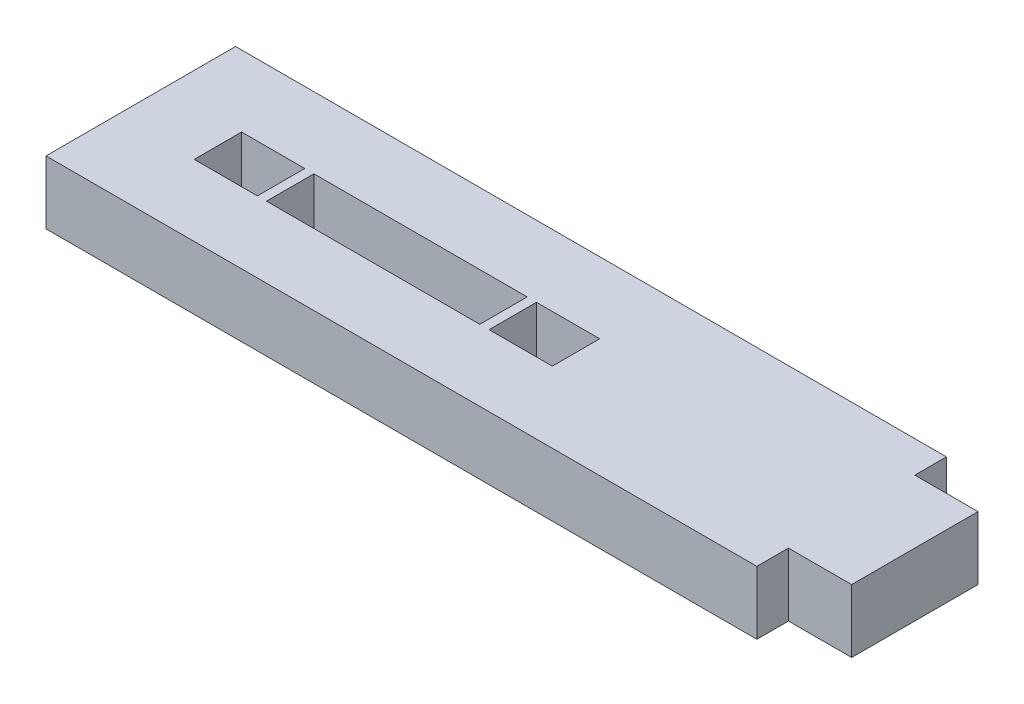
SolidWorks part; units mm, degrees
ref_plane "Front Plane" through (0, 0, 0) normal (0, 0, 1) x (1, 0, 0)
ref_plane "Top Plane" through (0, 0, 0) normal (0, 1, 0) x (1, 0, 0)
ref_plane "Right Plane" through (0, 0, 0) normal (1, 0, 0) x (0, 0, -1)
sketch "Sketch1" plane through (0, 0, 0) normal (0, 1, 0) x (1, 0, 0)
  line L1 (-22.5, -6) -> (22.5, -6)
  line L2 (-22.5, -6) -> (-22.5, 6)
  line L3 (-22.5, 6) -> (22.5, 6)
  line L4 (22.5, -6) -> (22.5, 6)
  line L5 (0, 6) -> (0, -6) construction
  line L6 (-22.5, 0) -> (22.5, 0) construction
  point P0 (0, 0)
  dimension "D1" = 45
  dimension "D2" = 12
extrude "Boss-Extrude1" add sketch "Sketch1" along normal blind 4
sketch "Sketch2" plane through (0, 0, 0) normal (0, 1, 0) x (1, 0, 0)
  line L0 (22.5, -6) -> (22.5, 6) construction
  line L1 (18.5, -4) -> (26.5, -4)
  line L2 (18.5, -4) -> (18.5, 4)
  line L3 (18.5, 4) -> (26.5, 4)
  line L4 (26.5, -4) -> (26.5, 4)
  line L5 (22.5, 4) -> (22.5, -4) construction
  line L6 (18.5, 0) -> (26.5, 0) construction
  point P0 (22.5, 0)
  dimension "D1" = 4
  dimension "D2" = 8
extrude "Boss-Extrude2" add sketch "Sketch2" along normal blind 4
sketch "Sketch4" plane through (0, 0, 0) normal (0, 1, 0) x (1, 0, 0)
  line L0 (-4.9, 6) -> (-4.9, -6) construction
  line L1 (22.5, 6) -> (-22.5, 6) construction
  line L2 (-22.5, -6) -> (22.5, -6) construction
  line L3 (22.5, 4) -> (22.5, 6) construction
  line L4 (1.05, 0) -> (5.05, 0)
  line L6 (-13.04, -1.5) -> (0.46, -1.5)
  line L7 (-13.04, -1.5) -> (-13.04, 1.5)
  line L8 (-13.04, 1.5) -> (0.46, 1.5)
  line L9 (0.46, -1.5) -> (0.46, 1.5)
  line L10 (-6.29, 1.5) -> (-6.29, -1.5) construction
  line L11 (-13.04, 0) -> (0.46, 0) construction
  point P11 (3.05, 0)
  point P12 (-6.29, 0)
  dimension "D1" = 27.4
  dimension "D2" = 4
  dimension "D3" = 7.95
  dimension "D4" = 3
  dimension "D5" = 13.5
  dimension "D6" = 1.39
extrude "Cut-Extrude2" cut sketch "Sketch4" along normal through all contours L6 L9 L8 L7 region at (-6.29, 0, 0)
extrude "Cut-Extrude-Thin2" cut sketch "Sketch4<3>" along normal blind 4 thin contours L4 thin type mid plane wall 3
sketch "Sketch4<3>" plane through (0, 0, 0) normal (0, 1, 0) x (1, 0, 0) same geometry as "Sketch4"
pattern_linear "LPattern1" count 2 spacing 18.67 along (-1, 0, 0) of "Cut-Extrude-Thin2"
